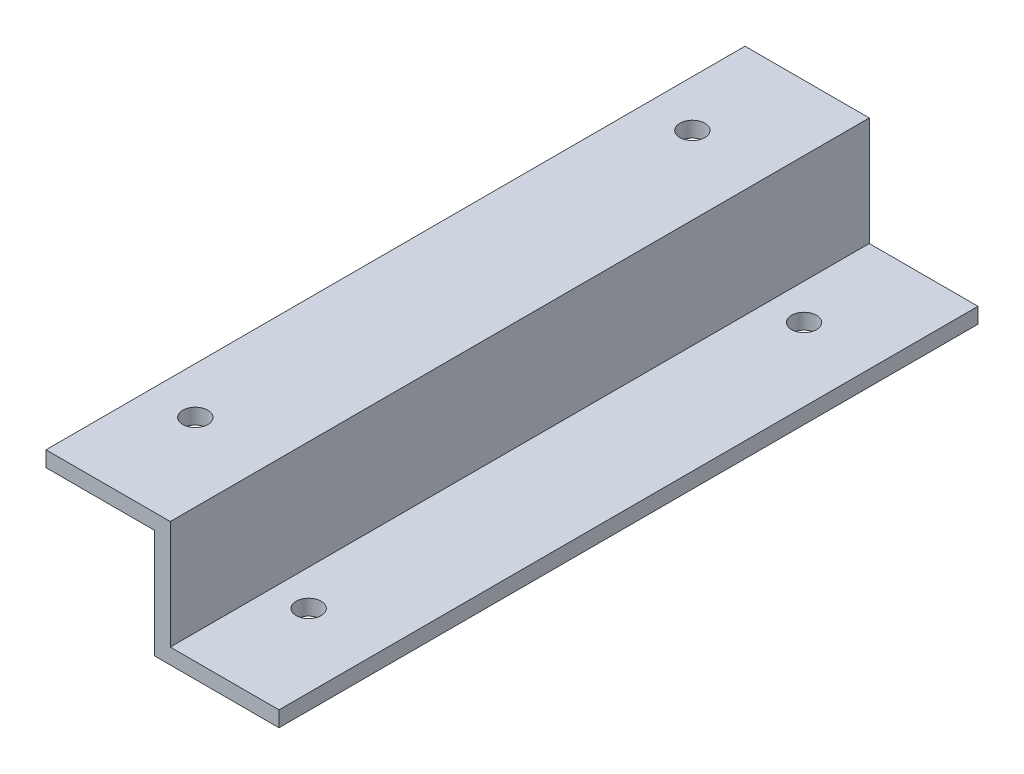
SolidWorks part; units mm, degrees
ref_plane "Front Plane" through (0, 0, 0) normal (0, 0, 1) x (1, 0, 0)
ref_plane "Top Plane" through (0, 0, 0) normal (0, 1, 0) x (1, 0, 0)
ref_plane "Right Plane" through (0, 0, 0) normal (1, 0, 0) x (0, 0, -1)
sketch "Sketch1" plane through (0, 0, 0) normal (0, 0, 1) x (1, 0, 0)
  line L0 (0, -11.1125) -> (0, 11.1125) construction
  line L1 (0, 11.1125) -> (-23.8125, 11.1125) construction
  line L2 (0, -11.1125) -> (23.8125, -11.1125) construction
  line L3 (1.5875, -9.525) -> (23.8125, -9.525) construction
  line L4 (1.5875, -9.525) -> (1.5875, 12.7) construction
  line L5 (1.5875, 12.7) -> (-23.8125, 12.7) construction
  line L6 (-1.5875, -12.7) -> (23.8125, -12.7) construction
  line L7 (-1.5875, -12.7) -> (-1.5875, 9.525) construction
  line L8 (-1.5875, 9.525) -> (-23.8125, 9.525) construction
  line L9 (-23.8125, 12.7) -> (-23.8125, 9.525) construction
  line L10 (23.8125, -9.525) -> (23.8125, -12.7) construction
  point P4 (0, 0)
  dimension "Leg Width" = 25.4
  dimension "Outside Height" = 25.4
  dimension "Wall Thickness" = 3.175
sketch "Sketch2" plane through (0, 0, 0) normal (1, 0, 0) x (0, 0, -1)
  line L0 (71.4375, 0) -> (-71.4375, 0) construction
  line L1 (0, 0) -> (0, 12.7) construction
  line L2 (-71.4375, 0) -> (-71.4375, 12.7) construction
  line L3 (71.4375, 0) -> (71.4375, 12.7) construction
  point P0 (-53.5781, 0)
  point P3 (53.5781, 0)
  point P4 (0, 0)
  dimension "D1" = 107.1562
  dimension "Length" = 142.875
sketch "Sketch3" plane through (0, 0, 0) normal (0, 0, 1) x (1, 0, 0)
  line L0 (23.8125, -9.525) -> (23.8125, -12.7) construction
  line L1 (1.5875, -9.525) -> (23.8125, -9.525) construction
  line L2 (-1.5875, -12.7) -> (23.8125, -12.7) construction
  line L3 (-1.5875, -12.7) -> (-1.5875, 9.525) construction
  line L4 (1.5875, -9.525) -> (1.5875, 12.7) construction
  line L5 (1.5875, 12.7) -> (-23.8125, 12.7) construction
  line L6 (-23.8125, 12.7) -> (-23.8125, 9.525) construction
  line L7 (-1.5875, 9.525) -> (-23.8125, 9.525) construction
  line L8 (23.8125, -9.525) -> (23.8125, -12.7)
  line L9 (1.5875, -9.525) -> (23.8125, -9.525)
  line L10 (-1.5875, -12.7) -> (23.8125, -12.7)
  line L11 (-1.5875, -12.7) -> (-1.5875, 9.525)
  line L12 (1.5875, -9.525) -> (1.5875, 12.7)
  line L13 (1.5875, 12.7) -> (-23.8125, 12.7)
  line L14 (-23.8125, 12.7) -> (-23.8125, 9.525)
  line L15 (-1.5875, 9.525) -> (-23.8125, 9.525)
extrude "Boss-Extrude1" add sketch "Sketch3" along normal up to vertex (71.4375 mm away) and the other way up to vertex (71.4375 mm away) up to point (0, 0, 71.4375) other way up to point (0, 0, -71.4375)
hole_wizard "#10 Clearance Hole1" positions "Sketch4" profile "Sketch5" hole size "#10" standard "ANSI Inch" end condition through all
sketch "Sketch4" plane through (0, 12.7, 0) normal (0, 1, 0) x (1, 0, 0)
  point P0 (-14.2875, -50.4444)
  point P3 (-14.2875, 51.1556)
sketch "Sketch5" plane through (-14.2875, 12.7, 50.4444) normal (1, 0, 0) x (0, 0, 1)
  line L0 (0, 0) -> (0, 25.4)
  line L1 (0, 25.4) -> (2.5527, 25.4)
  line L2 (2.5527, 25.4) -> (2.5527, 0)
  line L5 (2.5527, 0) -> (0, 0)
  line L11 (0, -6.35) -> (0, 107.95) construction
  dimension "Thru Hole Dia." = 5.1054
  dimension "Thru Hole Depth" = 25.4
sketch "Sketch7" plane through (0, -9.525, 0) normal (0, 1, 0) x (1, 0, 0)
  line L0 (-14.2875, -50.4444) -> (8.89, -50.4444) construction
  line L1 (8.89, -50.4444) -> (8.89, 50.7997) construction
hole_wizard "#10 Clearance Hole2" positions "Sketch8" profile "Sketch9" hole size "#10" standard "ANSI Inch" end condition through all
sketch "Sketch8" plane through (0, -9.525, 0) normal (0, 1, 0) x (1, 0, 0)
  point P0 (8.89, -50.4444)
  point P3 (8.89, 50.7997)
sketch "Sketch9" plane through (8.89, -9.525, 50.4444) normal (1, 0, 0) x (0, 0, 1)
  line L0 (0, 0) -> (0, 3.175)
  line L1 (0, 3.175) -> (2.5527, 3.175)
  line L2 (2.5527, 3.175) -> (2.5527, 0)
  line L5 (2.5527, 0) -> (0, 0)
  line L11 (0, -6.35) -> (0, 107.95) construction
  dimension "Thru Hole Dia." = 5.1054
  dimension "Thru Hole Depth" = 3.175
equation "\"D1@Sketch2\"=\"Length@Sketch2\"*0.75"
